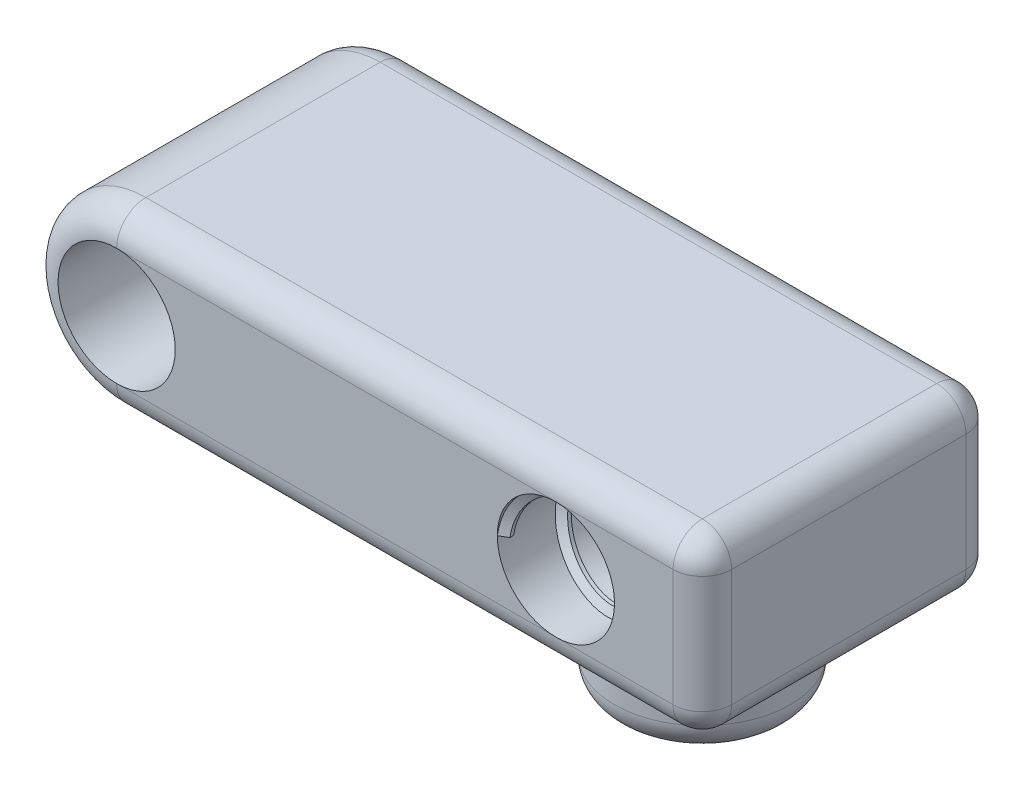
SolidWorks part; units mm, degrees
ref_plane "Front Plane" through (0, 0, 0) normal (0, 0, 1) x (1, 0, 0)
ref_plane "Top Plane" through (0, 0, 0) normal (0, 1, 0) x (1, 0, 0)
ref_plane "Right Plane" through (0, 0, 0) normal (1, 0, 0) x (0, 0, -1)
sketch "Sketch1" plane through (0, 0, 0) normal (0, 0, 1) x (1, 0, 0)
  circle A0 centre (0, 0) radius 15
  circle A1 centre (0, 0) radius 10
  dimension "D1" = 30
  dimension "D2" = 20
extrude "Boss-Extrude1" add sketch "Sketch1" along normal blind 50
ref_plane "Plane1" through (15, 0, 0) normal (1, 0, 0) x (0, 0, -1)
sketch "Sketch2" plane through (0, 0, 0) normal (0, 1, 0) x (1, 0, 0)
  line L0 (0, 0) -> (0, -50)
  line L1 (-15, -50) -> (15, -50) construction
  line L2 (0, -50) -> (100, -50)
  line L3 (100, -50) -> (100, 0)
  line L4 (100, 0) -> (0, 0)
  dimension "D1" = 100
extrude "Boss-Extrude2" add sketch "Sketch2" along normal blind 15 and the other way blind 15
sketch "Sketch3" plane through (0, 0, 50) normal (0, 0, 1) x (1, 0, 0)
  line L0 (0, -10) -> (0, 10) construction
  circle A0 centre (0, 0) radius 10
extrude "Cut-Extrude1" cut sketch "Sketch3" against normal through all both
sketch "Sketch4" plane through (0, -15, 0) normal (0, -1, 0) x (1, 0, 0)
  line L0 (100, 50) -> (100, 0) construction
  line L1 (0, 50) -> (100, 50) construction
  circle A0 centre (75, 25) radius 15
  circle A1 centre (75, 25) radius 10
  dimension "D1" = 30
  dimension "D4" = 20
  dimension "D2" = 25
  dimension "D3" = 25
extrude "Boss-Extrude3" add sketch "Sketch4" along normal blind 15
fillet "Fillet1" radius 5 1 edges at (75, -15, 40)
fillet "Fillet2" radius 5 1 edges at (100, 15, 25)
fillet "Fillet3" radius 5 1 edges at (100, -15, 25)
fillet "Fillet4" radius 5 12 edges at (98.5355, -13.5355, 0) (47.5, -15, 0) (-15, 0, 0) (47.5, 15, 0) (98.5355, 13.5355, 0) (98.5355, -13.5355, 50) (47.5, -15, 50) (-15, 0, 50) (47.5, 15, 50) (98.5355, 13.5355, 50) (100, 0, 0) (100, 0, 50)
fillet "Fillet5" radius 5 1 edges at (75, -30, 10)
sketch "Sketch6" plane through (0, 0, 50) normal (0, 0, 1) x (1, 0, 0)
  circle A0 centre (75, 0) radius 10
  dimension "D1" = 20
  dimension "D2" = 75
extrude "Cut-Extrude2" cut sketch "Sketch6" against normal blind 52
thread "Thread1" pitch 2.5 method extrude profile "Thread Profile1" start angle 0, offset 0, length 50, pitch 10, diameter 20
ref_plane "Plane2" through (65, 0, 50) normal (0, -1, 0) x (-1, 0, 0)
sketch "Thread Profile1" plane through (65, 0, 50) normal (0, -1, 0) x (-1, 0, 0)
  line L0 (0, 0) -> (0, 2.5) construction
  line L11 (0, 0) -> (0, 2.1875)
  line L12 (0, 2.1875) -> (-1.3532, 1.4062)
  line L13 (-1.3532, 1.4062) -> (-1.3532, 0.7812)
  line L15 (-1.3532, 0.7812) -> (0, 0)
  line L17 (-1.3532, 1.0937) -> (0, 1.0937) construction
  point P2 (0, 0)
  dimension "Pitch" = 2.5
  dimension "Profile_Angle" = 60
  dimension "Profile_Land" = 0.625
  dimension "Profile_Height" = 1.3532
sketch "Sketch9" plane through (100, 0, 0) normal (1, 0, 0) x (0, 0, -1)
  line L0 (0, -10) -> (0, 14.9653)
  line L1 (0, 14.9653) -> (11.1671, 14.9653)
  line L2 (11.1671, 14.9653) -> (11.1671, -16.383)
  line L3 (11.1671, -16.383) -> (0, -16.383)
  line L4 (0, -16.383) -> (0, -10)
extrude "Cut-Extrude3" cut sketch "Sketch9" against normal blind 52
